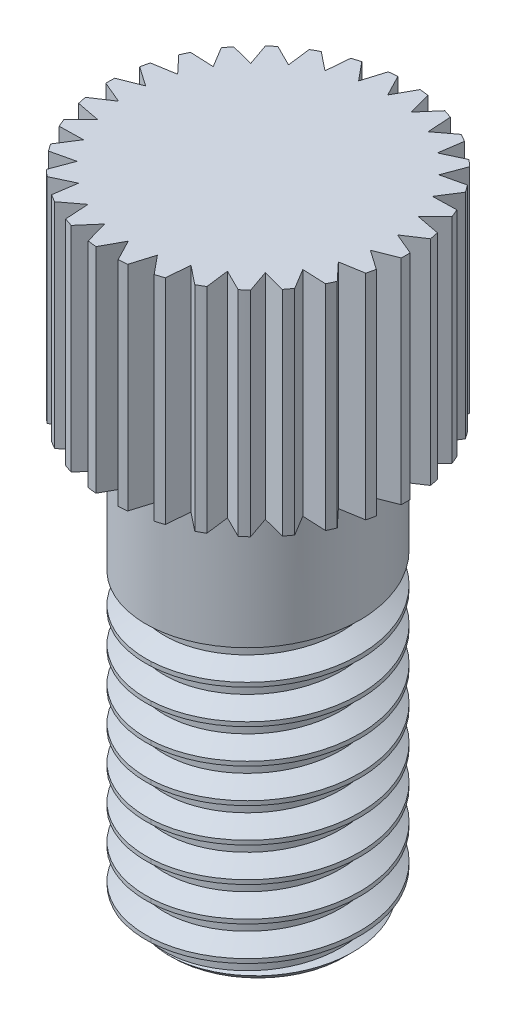
SolidWorks part; units mm, degrees
ref_plane "Ön Düzlem" through (0, 0, 0) normal (0, 0, 1) x (1, 0, 0)
ref_plane "Üst Düzlem" through (0, 0, 0) normal (0, 1, 0) x (1, 0, 0)
ref_plane "Sağ Düzlem" through (0, 0, 0) normal (1, 0, 0) x (0, 0, -1)
sketch "Çizim1" plane through (0, 0, 0) normal (0, 1, 0) x (1, 0, 0)
  line L0 (-2.2314, 2.6964) -> (-1.7338, 2.4482)
  line L1 (-1.7338, 2.4482) -> (-1.8028, 3)
  line L2 (-1.6221, 3.1014) -> (-1.1869, 2.7552)
  line L3 (-1.1869, 2.7552) -> (-1.1396, 3.3093)
  line L4 (-0.9418, 3.3709) -> (-0.5882, 2.9418)
  line L5 (-0.5882, 2.9418) -> (-0.4267, 3.4739)
  line L6 (-0.2204, 3.4931) -> (0.0363, 2.9998)
  line L7 (0.0363, 2.9998) -> (0.3049, 3.4867)
  line L8 (0.5107, 3.4625) -> (0.6592, 2.9267)
  line L9 (0.6592, 2.9267) -> (1.0231, 3.3471)
  line L10 (1.2194, 3.2807) -> (1.2533, 2.7257)
  line L11 (1.2533, 2.7257) -> (1.6967, 3.0612)
  line L12 (1.8749, 2.9555) -> (1.7926, 2.4055)
  line L13 (1.7926, 2.4055) -> (2.2961, 2.6416)
  line L14 (2.4484, 2.5011) -> (2.2536, 1.9803)
  line L15 (2.2536, 1.9803) -> (2.7951, 2.1065)
  line L16 (2.9149, 1.9374) -> (2.616, 1.4684)
  line L17 (2.616, 1.4684) -> (3.172, 1.4793)
  line L18 (3.254, 1.289) -> (2.8642, 0.8924)
  line L19 (2.8642, 0.8924) -> (3.4103, 0.7875)
  line L20 (3.4509, 0.5843) -> (2.9871, 0.2774)
  line L21 (2.9871, 0.2774) -> (3.4995, 0.0612)
  line L22 (3.497, -0.146) -> (2.9796, -0.3497)
  line L23 (2.9796, -0.3497) -> (3.4357, -0.6677)
  line L24 (3.3902, -0.8698) -> (2.8417, -0.9615)
  line L25 (2.8417, -0.9615) -> (3.2218, -1.3674)
  line L26 (3.1353, -1.5557) -> (2.5797, -1.5313)
  line L27 (2.5797, -1.5313) -> (2.8671, -2.0074)
  line L28 (2.7433, -2.1735) -> (2.205, -2.0342)
  line L29 (2.205, -2.0342) -> (2.3871, -2.5596)
  line L30 (2.2314, -2.6964) -> (1.7338, -2.4482)
  line L31 (1.7338, -2.4482) -> (1.8028, -3)
  line L32 (1.6221, -3.1014) -> (1.1869, -2.7552)
  line L33 (1.1869, -2.7552) -> (1.1396, -3.3093)
  line L34 (0.9418, -3.3709) -> (0.5882, -2.9418)
  line L35 (0.5882, -2.9418) -> (0.4267, -3.4739)
  line L36 (0.2204, -3.4931) -> (-0.0363, -2.9998)
  line L37 (-0.0363, -2.9998) -> (-0.3049, -3.4867)
  line L38 (-0.5107, -3.4625) -> (-0.6592, -2.9267)
  line L39 (-0.6592, -2.9267) -> (-1.0231, -3.3471)
  line L40 (-1.2194, -3.2807) -> (-1.2533, -2.7257)
  line L41 (-1.2533, -2.7257) -> (-1.6967, -3.0612)
  line L42 (-1.8749, -2.9555) -> (-1.7926, -2.4055)
  line L43 (-1.7926, -2.4055) -> (-2.2961, -2.6416)
  line L44 (-2.4484, -2.5011) -> (-2.2536, -1.9803)
  line L45 (-2.2536, -1.9803) -> (-2.7951, -2.1065)
  line L46 (-2.9149, -1.9374) -> (-2.616, -1.4684)
  line L47 (-2.616, -1.4684) -> (-3.172, -1.4793)
  line L48 (-3.254, -1.289) -> (-2.8642, -0.8924)
  line L49 (-2.8642, -0.8924) -> (-3.4103, -0.7875)
  line L50 (-3.4509, -0.5843) -> (-2.9871, -0.2774)
  line L51 (-2.9871, -0.2774) -> (-3.4995, -0.0612)
  line L52 (-3.497, 0.146) -> (-2.9796, 0.3497)
  line L53 (-2.9796, 0.3497) -> (-3.4357, 0.6677)
  line L54 (-3.3902, 0.8698) -> (-2.8417, 0.9615)
  line L55 (-2.8417, 0.9615) -> (-3.2218, 1.3674)
  line L56 (-3.1353, 1.5557) -> (-2.5797, 1.5313)
  line L57 (-2.5797, 1.5313) -> (-2.8671, 2.0074)
  line L58 (-2.7433, 2.1735) -> (-2.205, 2.0342)
  line L59 (-2.205, 2.0342) -> (-2.3871, 2.5596)
  circle A0 centre (0, 0) radius 3.5
  point P22 (0, 0)
  dimension "D1" = 7
  dimension "D3" = 30
extrude "Yükseklik-Ekstrüzyon2" add sketch "Çizim1" along normal blind 5 contours L36 A0 L35 L34 L33 L32 L31 L30 L29 L28 L27 L26 L25 L24 L23 L22 L21 L20 L19 L18 L17 L16 L15 L14 L13 L12 L11 L10 L9 L8 L7 L6 L5 L4 L3
sketch "Çizim2" plane through (0, 0, 0) normal (0, -1, 0) x (1, 0, 0)
  circle A0 centre (0, 0) radius 2.5
extrude "Yükseklik-Ekstrüzyon3" add sketch "Çizim2" along normal blind 10
chamfer "Pah1" distance 0.5 angle 45 1 edges at (0, -10, -2.5)
sketch "Çizim7" plane through (0, -10, 0) normal (0, -1, 0) x (1, 0, 0)
  circle A0 centre (0, 0) radius 2.5
  dimension "D1" = 5
curve "Helis/Spiral1" pitch 0.8 height 7 turns 8.75
ref_plane "Düzlem1" through (-2.5, -10, 0) normal (0, 0.0509, 0.9987) x (1, 0, 0)
sketch "Çizim9" plane through (-2.5, -10, 0) normal (0, 0.0509, 0.9987) x (1, 0, 0)
  line L0 (0.433, 0.1) -> (0.433, -0.1)
  line L1 (0.433, -0.1) -> (0, -0.35)
  line L2 (0, -0.35) -> (0, 0.35)
  line L3 (0.433, 0) -> (-0.5068, 0) construction
  line L4 (0.433, 0.1) -> (0, 0.35)
  point P6 (0, 0)
  dimension "D1" = 0.2
  dimension "D2" = 0.433
  dimension "D3" = 60
sweep "Kes-Süpür2" cut profiles "Çizim9" path "Helis/Spiral1"
